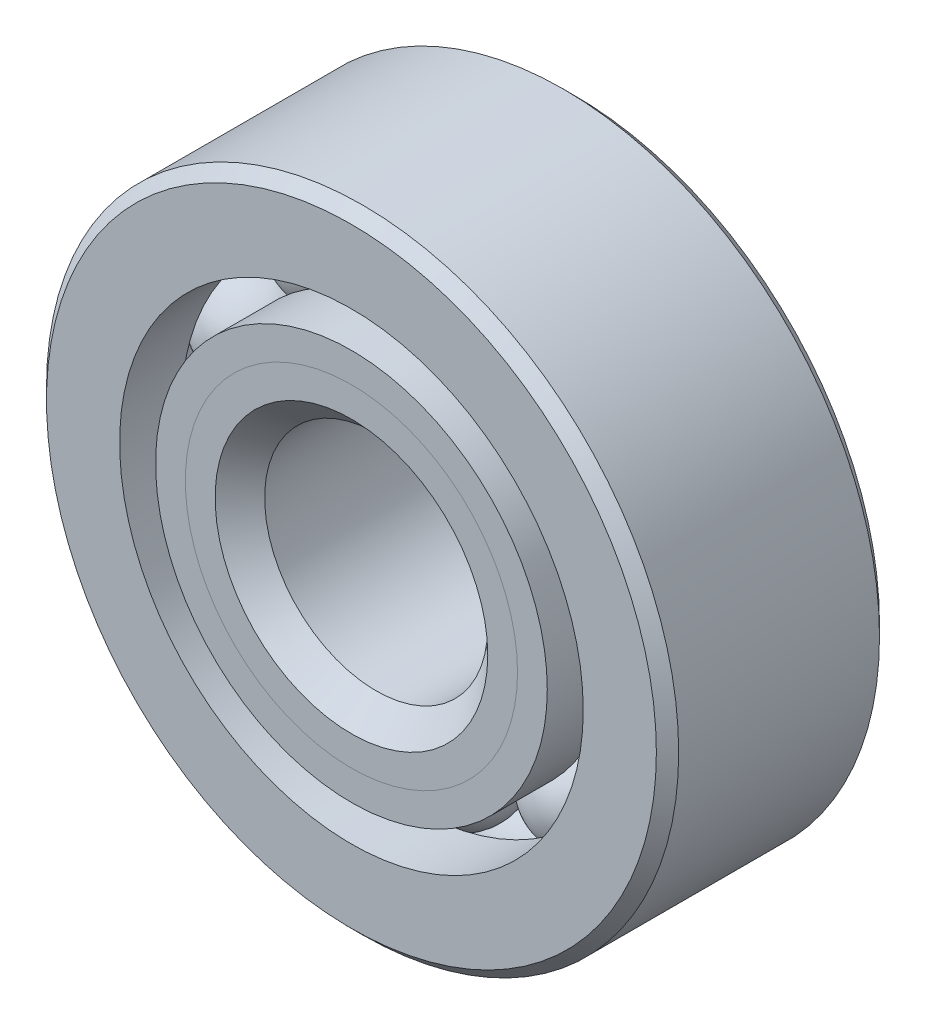
SolidWorks part; units mm, degrees
ref_plane "Front Plane" through (0, 0, 0) normal (0, 0, 1) x (1, 0, 0)
ref_plane "Top Plane" through (0, 0, 0) normal (0, 1, 0) x (1, 0, 0)
ref_plane "Right Plane" through (0, 0, 0) normal (1, 0, 0) x (0, 0, -1)
sketch "Sketch1" plane through (0, 0, 0) normal (1, 0, 0) x (0, 0, -1)
  line L0 (-3, 0) -> (3, 0) construction
  line L1 (0, 8.5) -> (0, -8.5) construction
  line L2 (2.7, 8.5) -> (-2.7, 8.5)
  line L3 (-2.7, 8.5) -> (-3, 8.2)
  line L4 (-3, 8.2) -> (-3, 6.2335)
  line L5 (-3, 6.2335) -> (-1.3333, 6.2335)
  line L6 (3, 6.2335) -> (1.3333, 6.2335)
  line L7 (3, 8.2) -> (3, 6.2335)
  line L8 (2.7, 8.5) -> (3, 8.2)
  line L9 (0, 8.5) -> (0, 5.75) construction
  line L10 (0, 5.75) -> (0, 3) construction
  line L11 (-3, -8.5) -> (3, -8.5) construction
  arc A0 (-1.3333, 6.2335) -> (1.3333, 6.2335) centre (0, 5.75) cw
  point P14 (0, 3)
  point P19 (0, -8.5)
  point P20 (0, -8.5)
  dimension "OD" = 17
  dimension "D1" = 45
  dimension "D2" = 0.3
  dimension "D3" = 2.6667
  dimension "D4" = 0.4835
  dimension "Width" = 6
revolve "Revolve1" add sketch "Sketch1" angle 360 about L0
sketch "Sketch2" plane through (0, 0, 0) normal (1, 0, 0) x (0, 0, -1)
  line L0 (-3, 5.2665) -> (-1.3333, 5.2665)
  line L1 (-3, 8.2) -> (-3, -8.2) construction
  line L2 (-3, 5.2665) -> (-3, 4.4662)
  line L3 (-3, 4.4662) -> (-2.1997, 3.6659)
  line L4 (-2.1997, 3.6659) -> (0, 3.6659)
  line L5 (0, 8.5) -> (0, -8.5) construction
  line L6 (0, 3.6659) -> (0, 4.3317)
  line L7 (0, 4.3317) -> (0, 3) construction
  line L8 (-3, 5.2665) -> (-3, 3.6659) construction
  line L9 (-3, 3.6659) -> (-2.1997, 3.6659) construction
  arc A0 (-1.3333, 5.2665) -> (0, 4.3317) centre (0, 5.75) ccw
  arc A1 (1.3333, 6.2335) -> (-1.3333, 6.2335) centre (0, 5.75) ccw construction
  circle A2 centre (0, 5.75) radius 1.4183 construction
  dimension "D1" = 45
revolve "Revolve2" add sketch "Sketch2" angle 360 about L0
sketch "Sketch3" plane through (0, 0, 0) normal (1, 0, 0) x (0, 0, -1)
  line L0 (-3, 4.4662) -> (-2.1997, 3.6659)
  line L1 (-2.1997, 3.6659) -> (0, 3.6659)
  line L2 (0, 3.6659) -> (0, 4.3317)
  line L3 (-3, 4.4662) -> (-3, 3.6659)
  line L4 (-3, 5.2665) -> (-3, 3.6659) construction
  line L5 (-3, 3.6659) -> (-2.3341, 3)
  line L6 (-2.3341, 3) -> (2.7, 3)
  line L7 (2.7, 8.5) -> (2.7, -8.5) construction
  line L8 (2.7, 3) -> (3, 3.3)
  line L9 (3, -8.2) -> (3, 8.2) construction
  line L10 (3, 3.3) -> (3, 5.2665)
  line L11 (3, 5.2665) -> (1.3333, 5.2665)
  line L13 (2.7, 8.5) -> (3, 8.2) construction
  circle A0 centre (0, 5.75) radius 1.4183 construction
  arc A1 (1.3333, 5.2665) -> (0, 4.3317) centre (0, 5.75) cw
revolve "Revolve3" add sketch "Sketch3" angle 360 about L0
sketch "Sketch4" plane through (0, 0, 0) normal (1, 0, 0) x (0, 0, -1)
  line L0 (-1.4183, 5.75) -> (1.4183, 5.75)
  circle A1 centre (0, 5.75) radius 1.4183 construction
  arc A2 (-1.4183, 5.75) -> (1.4183, 5.75) centre (0, 5.75) cw
  arc A3 (1.3333, 6.2335) -> (-1.3333, 6.2335) centre (0, 5.75) ccw construction
revolve "Revolve4" add sketch "Sketch4" angle 360 about L0
ref_axis "Axis1" through (0, 0, -3) along (0, 0, 1)
pattern_circular "CirPattern1" count 10 every 36 about axis through (0, 0, -3) along (0, 0, 1) of bodies 104
ref_axis "Center Axis 1" through (0, 0, -2.7) along (0, 0, 1)
equation "\"D2@Sketch1\" = \"Width@Sketch1\"*.05"
equation "\"D3@Sketch1\" = \"Width@Sketch1\"/2.25"
equation "\"D4@Sketch1\" = (((\"OD@Sketch1\"-\"Width@Sketch1\")/2)/3.25)/3.5"
equation "\"D2@CirPattern1\" = 360/\"Balls@CirPattern1\""
